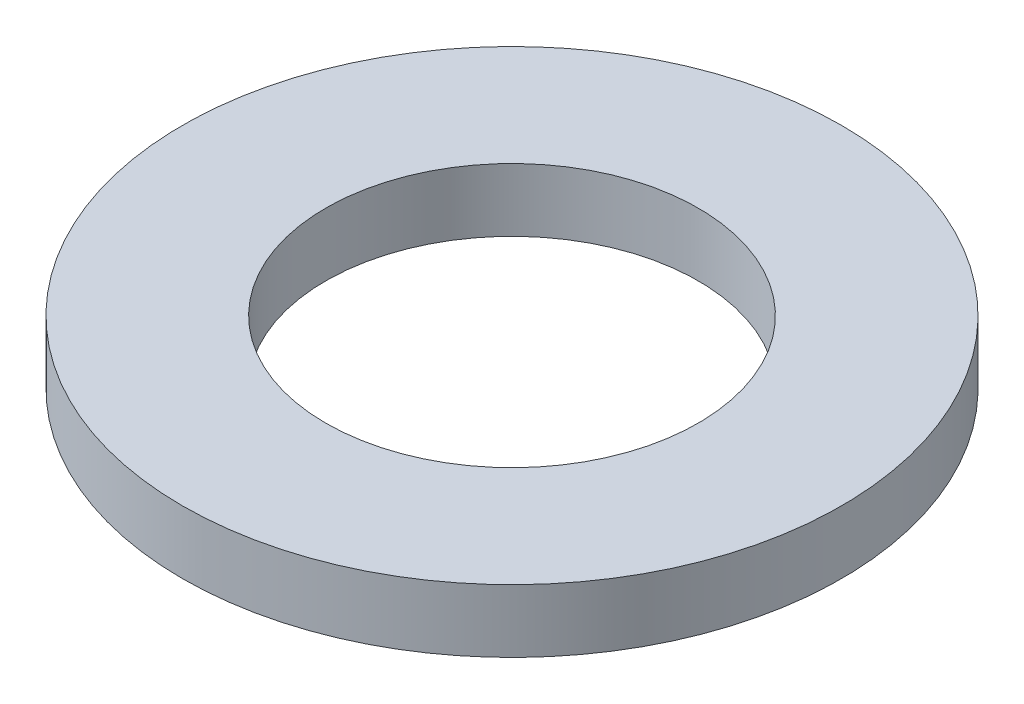
SolidWorks part; units mm, degrees
ref_plane "Front Plane" through (0, 0, 0) normal (0, 0, 1) x (1, 0, 0)
ref_plane "Top Plane" through (0, 0, 0) normal (0, 1, 0) x (1, 0, 0)
ref_plane "Right Plane" through (0, 0, 0) normal (1, 0, 0) x (0, 0, -1)
sketch "Sketch1" plane through (0, 0, 0) normal (0, 1, 0) x (1, 0, 0)
  circle A0 centre (0, 0) radius 57.5
  dimension "FLANGE_OD" = 115
extrude "Boss-Extrude1" add sketch "Sketch1" along normal blind 11
sketch "Sketch2" plane through (0, 0, 0) normal (0, 1, 0) x (1, 0, 0)
  circle A0 centre (0, 0) radius 32.5
  dimension "BORE_D" = 65
extrude "Cut-Extrude1" cut sketch "Sketch2" along normal through all
sketch "Sketch3" plane through (0, 11, 0) normal (0, 1, 0) x (1, 0, 0)
  circle A0 centre (0, 0) radius 24.4796 construction
  circle A1 centre (-24.4796, 0) radius 3.4684
  dimension "BOLT_D" = 6.9368
  dimension "BOLT_PCD" = 48.9593
extrude "Cut-Extrude2" cut sketch "Sketch3" against normal blind 8.8404 rebuild error yes
pattern_circular "CirPattern1" count 8 over 360 rebuild error yes
